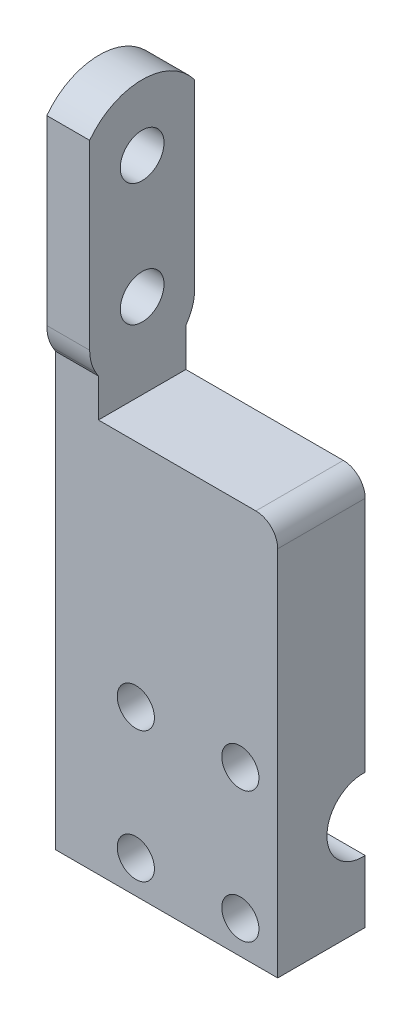
SolidWorks part; units mm, degrees
ref_plane "Front Plane" through (0, 0, 0) normal (0, 0, 1) x (1, 0, 0)
ref_plane "Top Plane" through (0, 0, 0) normal (0, 1, 0) x (1, 0, 0)
ref_plane "Right Plane" through (0, 0, 0) normal (1, 0, 0) x (0, 0, -1)
sketch "Sketch4" plane through (0, 0, 0) normal (0, 0, 1) x (1, 0, 0)
  line L0 (0, 0) -> (-11.95, -14.95) construction
  line L1 (-20.5, 22.5) -> (20.5, 22.5)
  line L2 (-20.5, 22.5) -> (-20.5, -22.5)
  line L3 (-20.5, -22.5) -> (20.5, -22.5)
  line L4 (20.5, 22.5) -> (20.5, -22.5)
  line L5 (0, 0) -> (11.95, -14.95) construction
  line L6 (0, 0) -> (11.95, 14.95) construction
  line L7 (-11.95, 14.95) -> (11.95, 14.95) construction
  line L8 (-11.95, 14.95) -> (-11.95, -14.95) construction
  line L9 (-11.95, -14.95) -> (11.95, -14.95) construction
  line L10 (11.95, 14.95) -> (11.95, -14.95) construction
  circle A4 centre (-11.95, 14.95) radius 4.25
  circle A5 centre (11.95, 14.95) radius 4.25
  circle A6 centre (11.95, -14.95) radius 4.25
  circle A7 centre (-11.95, -14.95) radius 4.25
  point P0 (0, 0)
  point P6 (0, 0)
  dimension "D3" = 8.5
  dimension "D4" = 23.9
  dimension "D1" = 41
  dimension "D2" = 45
  dimension "D5" = 29.9
extrude "Boss-Extrude1" add sketch "Sketch4" along normal blind 20
sketch "Sketch6" plane through (0, 0, 0) normal (0, 0, -1) x (-1, 0, 0)
  line L2 (20.5, -22.5) -> (20.5, 129.9)
  line L3 (20.5, 129.9) -> (30.3, 129.9)
  line L4 (30.3, 129.9) -> (30.3, -22.5)
  line L5 (30.3, -22.5) -> (20.5, -22.5)
  line L6 (-20.5, -22.5) -> (-20.5, 22.5) construction
  dimension "D1" = 50.8
  dimension "D2" = 152.4
extrude "Boss-Extrude2" add sketch "Sketch6" against normal blind 20
sketch "Sketch7" plane through (-20.5, 0, 0) normal (1, 0, 0) x (0, 0, -1)
  line L0 (-10, 129.9) -> (-10, 22.5) construction
  line L1 (-20, 129.9) -> (0, 129.9) construction
  line L2 (-20, 22.5) -> (0, 22.5) construction
  line L3 (0, 76.2) -> (0.5838, 77.1769)
  line L5 (0, 129.9) -> (0, 22.5) construction
  line L6 (2, 82.307) -> (2, 123.8853)
  line L7 (0.2383, 129.5537) -> (0, 129.9)
  line L8 (0, 76.2) -> (0, 129.9)
  line L9 (-20, 76.2) -> (-20.5838, 77.1769)
  line L10 (-22, 82.307) -> (-22, 123.8853)
  line L11 (-20.2383, 129.5537) -> (-20, 129.9)
  line L12 (-20, 76.2) -> (-20, 129.9)
  circle A0 centre (-10, 114.9) radius 5
  circle A1 centre (-10, 86.9) radius 5
  arc A2 (-20.5838, 77.1769) -> (-22, 82.307) centre (-12, 82.307) cw
  arc A3 (0.5838, 77.1769) -> (2, 82.307) centre (-8, 82.307) ccw
  arc A4 (2, 123.8853) -> (0.2383, 129.5537) centre (-8, 123.8853) ccw
  arc A5 (-22, 123.8853) -> (-20.2383, 129.5537) centre (-12, 123.8853) cw
  point P23 (-22, 79.5465)
  point P26 (2, 79.5465)
  point P29 (2, 126.9932)
  point P32 (-22, 126.9932)
  dimension "D1" = 28
  dimension "D2" = 10
  dimension "D4" = 10
  dimension "D5" = 15
  dimension "D3" = 12
extrude "Boss-Extrude3" add sketch "Sketch7" along direction (-1, 0, 0) on the side against the normal up to surface (9.8 mm away) up to face at (-30.3, 53.7, 10)
sketch "Sketch8" plane through (-20.5, 0, 0) normal (1, 0, 0) x (0, 0, -1)
  circle A1 centre (-10, 86.9) radius 5
  circle A2 centre (-10, 86.9) radius 5
  circle A3 centre (-10, 114.9) radius 5
  circle A4 centre (-10, 114.9) radius 5
  dimension "D1" = 0
  dimension "D2" = 0
extrude "Cut-Extrude2" cut sketch "Sketch8" against normal blind 15
sketch "Sketch5" plane through (20.5, 0, 0) normal (1, 0, 0) x (0, 0, -1)
  line L2 (0, -22.5) -> (0, 22.5) construction
  circle A0 centre (-0.5, 0) radius 8.25
  dimension "D1" = 16.5
  dimension "D2" = 0.5
extrude "Cut-Extrude1" cut sketch "Sketch5" against normal blind 65
sketch "Sketch9" plane through (0, 0, 0) normal (0, 0, -1) x (-1, 0, 0)
  line L2 (-20.5, 22.5) -> (-20.5, 62.5)
  line L6 (-15.5, 67.5) -> (20.5, 67.5)
  line L7 (20.5, 76.2) -> (20.5, 22.5) construction
  line L8 (-20.5, 22.5) -> (20.5, 22.5)
  line L14 (20.5, 22.5) -> (20.5, 67.5)
  line L15 (20.5, 67.5) -> (-20.5, 22.5) construction
  line L16 (-11.5622, 45) -> (11.5622, 45) construction
  arc A1 (-20.5, 62.5) -> (-15.5, 67.5) centre (-15.5, 62.5) cw
  point P6 (0, 45)
  point P8 (0, 45)
  point P9 (20.5, 22.5)
  dimension "D1" = 5
extrude "Boss-Extrude4" add sketch "Sketch9" against normal up to surface (20 mm away) up to face at (-10.1, 25.4, 20)
ref_axis "Axis1" through (-30.3, 0, 0.5) along (1, 0, 0)
sketch "Sketch10" plane through (0, 0, 0) normal (0, 0, 1) x (1, 0, 0)
  line L0 (-30.3, -22.5) -> (-26.3, -22.5)
  line L1 (-30.3, -22.5) -> (-20.5, -22.5) construction
  line L2 (-26.3, -22.5) -> (-26.3, 157.5939)
  line L3 (-26.3, 157.5939) -> (-61.0758, 162.5234)
  line L4 (-61.0758, 162.5234) -> (-64.5228, 37.5847)
  line L5 (-64.5228, 37.5847) -> (-30.3, -22.5)
extrude "Cut-Extrude3" cut sketch "Sketch10" along normal blind 86 and the other way blind 86
sketch "Sketch11" plane through (-26.3, 0, 0) normal (-1, 0, 0) x (0, 0, 1)
  line L0 (0, -8.2348) -> (0, 8.2348)
  arc A0 (0, -8.2348) -> (0, 8.2348) centre (0.5, 0) ccw construction
  arc A1 (0, -8.2348) -> (0, 8.2348) centre (0.5, 0) ccw
extrude "Boss-Extrude5" add sketch "Sketch11" against normal blind 1.5
sketch "Sketch12" plane through (-20.5, 0, 0) normal (1, 0, 0) x (0, 0, -1)
  line L0 (-22, 123.8853) -> (-30.8203, 123.8853)
  line L1 (-30.8203, 123.8853) -> (-25.069, 136.8187)
  line L2 (-25.069, 136.8187) -> (-2.4795, 134.9128)
  line L3 (-2.4795, 134.9128) -> (8.9971, 125.2643)
  line L4 (8.9971, 125.2643) -> (2, 123.8853)
  arc A0 (-22, 123.8853) -> (2, 123.8853) centre (-10, 114.922) cw
extrude "Cut-Extrude4" cut sketch "Sketch12" against normal blind 13.5
sketch "Sketch13" plane through (-26.3, 0, 0) normal (-1, 0, 0) x (0, 0, 1)
  line L7 (0, -22.5) -> (20, -22.5)
  line L8 (20, -22.5) -> (20, 76.2)
  line L9 (20, 76.2) -> (20.5838, 77.1769)
  line L10 (22, 82.307) -> (22, 123.8853)
  line L11 (-2, 123.8853) -> (-2, 82.307)
  line L12 (-0.5838, 77.1769) -> (0, 76.2)
  line L13 (0, 76.2) -> (0, -22.5)
  line L14 (0, -22.5) -> (20, -22.5)
  line L15 (20, -22.5) -> (20, 76.2)
  line L16 (20, 76.2) -> (20.5838, 77.1769)
  line L17 (22, 82.307) -> (22, 123.8853)
  line L18 (-2, 123.8853) -> (-2, 82.307)
  line L19 (-0.5838, 77.1769) -> (0, 76.2)
  line L20 (0, 76.2) -> (0, -22.5)
  circle A0 centre (10, 114.9) radius 5 construction
  circle A1 centre (10, 86.9) radius 5 construction
  circle A2 centre (10, 114.9) radius 5
  circle A3 centre (10, 86.9) radius 5
  arc A6 (20.5838, 77.1769) -> (22, 82.307) centre (12, 82.307) ccw
  arc A7 (22, 123.8853) -> (-2, 123.8853) centre (10, 114.922) ccw
  arc A8 (-2, 82.307) -> (-0.5838, 77.1769) centre (8, 82.307) ccw
  arc A11 (20.5838, 77.1769) -> (22, 82.307) centre (12, 82.307) ccw
  arc A12 (22, 123.8853) -> (-2, 123.8853) centre (10, 114.922) ccw
  arc A13 (-2, 82.307) -> (-0.5838, 77.1769) centre (8, 82.307) ccw
  dimension "D1" = 0
extrude "Boss-Extrude6" add sketch "Sketch13" along normal blind 4
sketch "Sketch14" plane through (-30.3, 0, 0) normal (-1, 0, 0) x (0, 0, 1)
  circle A0 centre (0, 0) radius 4
extrude "Cut-Extrude5" cut sketch "Sketch14" against normal blind 10
sketch "Sketch16" plane through (0, 0, 0) normal (0, 0, -1) x (-1, 0, 0)
  line L0 (-7.3376, 35.8832) -> (8.2818, 54.1053)
  line L1 (-2.6745, 59.1133) -> (5.9785, 59.1133)
  line L2 (-12.6745, 49.1133) -> (-12.6745, 37.8575)
  line L5 (-12.6745, 59.1133) -> (2.6737, 41.6277) construction
  line L6 (30.3, 67.5) -> (-20.5, 8.2348) construction
  line L10 (30.3, 76.2) -> (30.3, 4) construction
  line L11 (4.245, 32.065) -> (11.2546, 40.2427)
  line L12 (6.5228, 27.1126) -> (13.5324, 27.1126)
  line L13 (16.5324, 30.1126) -> (16.5324, 38.2903)
  arc A0 (-2.6745, 59.1133) -> (-12.6745, 49.1133) centre (-2.6745, 49.1133) ccw
  arc A5 (8.2818, 54.1053) -> (5.9785, 59.1133) centre (5.9785, 56.0796) ccw
  arc A6 (-7.3376, 35.8832) -> (-12.6745, 37.8575) centre (-9.6409, 37.8575) cw
  arc A7 (13.5324, 27.1126) -> (16.5324, 30.1126) centre (13.5324, 30.1126) ccw
  arc A8 (11.2546, 40.2427) -> (16.5324, 38.2903) centre (13.5324, 38.2903) cw
  arc A9 (4.245, 32.065) -> (6.5228, 27.1126) centre (6.5228, 30.1126) ccw
  point P0 (2.6737, 41.6277)
  point P15 (0, 27.1126)
  point P16 (-9.5327, 27.1126)
  point P22 (12.5745, 59.1133)
  point P25 (-12.6745, 29.6569)
  dimension "D1" = 10
  dimension "D3" = 3
  dimension "D2" = 8
extrude "Cut-Extrude6" cut sketch "Sketch16" against normal blind 15
